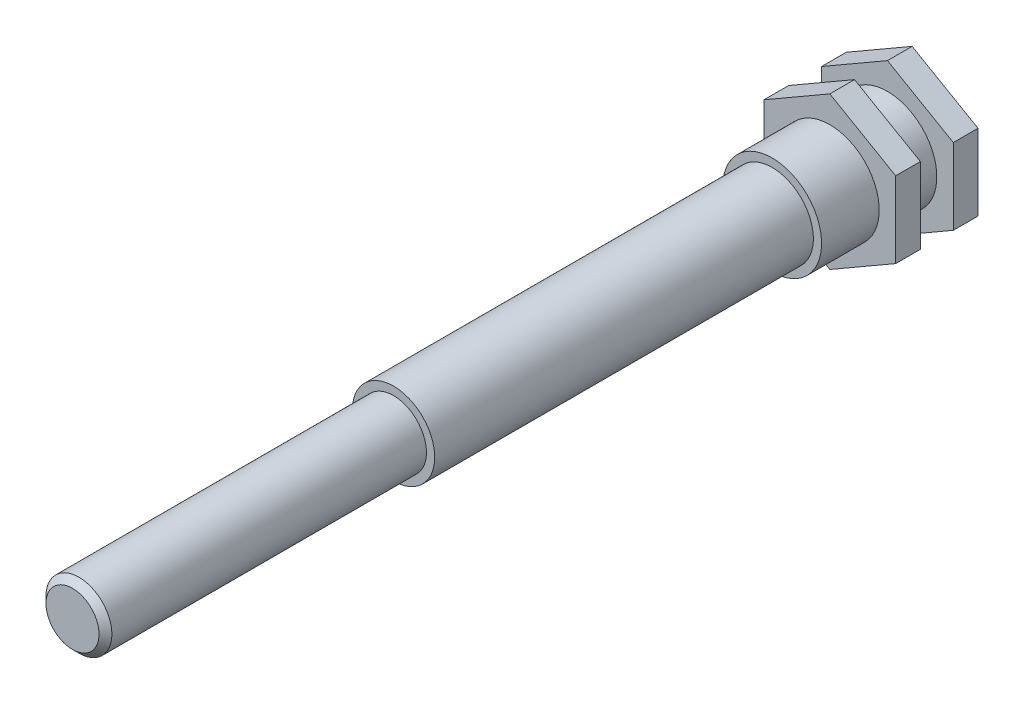
SolidWorks part; units mm, degrees
material "Латунь"
ref_plane "Спереди" through (0, 0, 0) normal (0, 0, 1) x (1, 0, 0)
ref_plane "Сверху" through (0, 0, 0) normal (0, 1, 0) x (1, 0, 0)
ref_plane "Справа" through (0, 0, 0) normal (1, 0, 0) x (0, 0, -1)
sketch "Эскиз1" plane through (0, 0, 0) normal (0, 0, 1) x (1, 0, 0)
  line L1 (-4, 2.3094) -> (-4, -2.3094)
  line L2 (-4, -2.3094) -> (0, -4.6188)
  line L3 (0, -4.6188) -> (4, -2.3094)
  line L4 (4, -2.3094) -> (4, 2.3094)
  line L5 (4, 2.3094) -> (0, 4.6188)
  line L6 (0, 4.6188) -> (-4, 2.3094)
  circle A0 centre (0, 0) radius 4 construction
  dimension "D1" = 8
extrude "Бобышка-Вытянуть1" add sketch "Эскиз1" along normal blind 1.5
sketch "Эскиз2" plane through (0, 0, 1.5) normal (0, 0, 1) x (1, 0, 0)
  circle A0 centre (0, 0) radius 3
  dimension "D1" = 6
extrude "Бобышка-Вытянуть2" add sketch "Эскиз2" along normal blind 7
extrude "Бобышка-Вытянуть3" add sketch "Эскиз1<2>" along normal blind 1.5 from offset 3.5
sketch "Эскиз1<2>" plane through (0, 0, 0) normal (0, 0, 1) x (1, 0, 0) same geometry as "Эскиз1"
sketch "Эскиз3" plane through (0, 0, 8.5) normal (0, 0, 1) x (1, 0, 0)
  circle A0 centre (0, 0) radius 2.5
  dimension "D1" = 5
extrude "Бобышка-Вытянуть4" add sketch "Эскиз3" along normal blind 23
sketch "Эскиз4" plane through (0, 0, 31.5) normal (0, 0, 1) x (1, 0, 0)
  circle A0 centre (0, 0) radius 2
  dimension "D1" = 4
extrude "Бобышка-Вытянуть5" add sketch "Эскиз4" along normal blind 19.5
cosmetic thread "Условное изображение резьбы1" parameters "D2"=3.22
chamfer "Фаска1" distance 0.39 angle 45 1 edges at (2, 0, 51)
